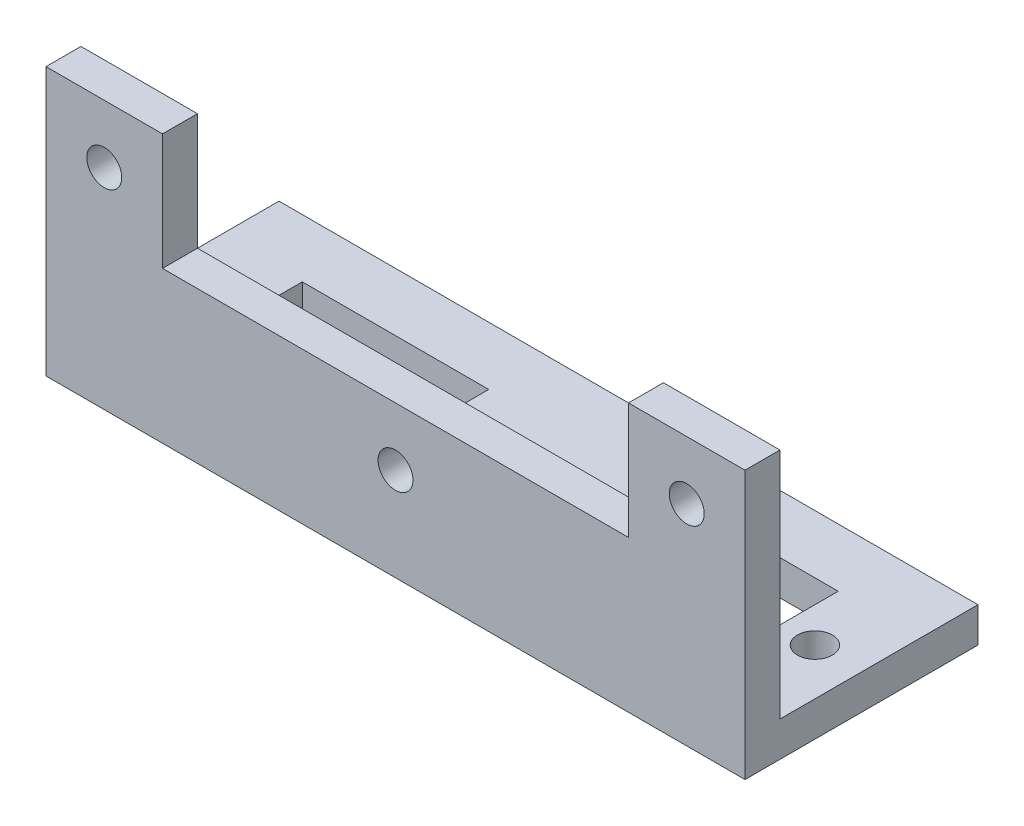
SolidWorks part; units mm, degrees
ref_plane "Front Plane" through (0, 0, 0) normal (0, 0, 1) x (1, 0, 0)
ref_plane "Top Plane" through (0, 0, 0) normal (0, 1, 0) x (1, 0, 0)
ref_plane "Right Plane" through (0, 0, 0) normal (1, 0, 0) x (0, 0, -1)
sketch "Sketch1" plane through (0, 0, 0) normal (0, 1, 0) x (1, 0, 0)
  line L0 (0, 127) -> (-76.2, 127)
  line L1 (0, 0) -> (406.4, 0)
  line L2 (0, 0) -> (0, 254)
  line L3 (0, 254) -> (406.4, 254)
  line L4 (406.4, 0) -> (406.4, 254)
  line L5 (406.4, 127) -> (482.6, 127)
  line L6 (482.6, 127) -> (685.8, 127)
  line L7 (762, 127) -> (685.8, 127)
  line L8 (1168.4, 127) -> (1244.6, 127)
  line L9 (762, 0) -> (1168.4, 0)
  line L10 (762, 0) -> (762, 254)
  line L11 (1168.4, 0) -> (1168.4, 254)
  line L12 (762, 254) -> (1168.4, 254)
  line L13 (-114.3, 127) -> (-177.8, 127)
  line L14 (-177.8, 127) -> (-177.8, 381)
  line L15 (1282.7, 127) -> (1346.2, 127)
  line L16 (1346.2, 127) -> (1346.2, -127)
  line L18 (-177.8, 381) -> (1346.2, 381)
  line L19 (-177.8, 381) -> (-177.8, -127)
  line L20 (-177.8, -127) -> (1346.2, -127)
  line L21 (1346.2, 381) -> (1346.2, -127)
  circle A0 centre (-76.2, 127) radius 38.1
  circle A1 centre (482.6, 127) radius 38.1
  circle A2 centre (1244.6, 127) radius 38.1
  circle A3 centre (685.8, 127) radius 38.1
extrude "Boss-Extrude2" add sketch "Sketch1" along normal blind 76.2 contours A3 L7 L10 L12 L11 L8 A2 L15 L21 L18 L14 L13 A0 L0 L2 L3 L4 L5 A1 L6 | A3 L6 A1 L5 L4 L1 L2 L0 A0 L13 L19 L20 L16 L15 A2 L8 L11 L9 L10 L7 region at (584.2, 0, 27.5366) region at (584.2, 0, -281.5366)
scale "Scale2" scale about centroid uniform scaling yes scale factor 0.03937
sketch "Sketch2" plane through (0, 39.6, 0) normal (0, 1, 0) x (1, 0, 0)
  line L0 (569.2, 132) -> (569.2, 122)
  line L1 (561.2, 132) -> (577.2, 132) construction
  line L2 (561.2, 122) -> (577.2, 122) construction
  line L3 (599.2, 132) -> (599.2, 122)
  line L4 (591.2, 132) -> (607.2, 132) construction
  line L5 (591.2, 122) -> (607.2, 122) construction
  line L6 (569.2, 127) -> (599.2, 127)
sketch "Sketch3" plane through (0, 0, -117) normal (0, 0, 1) x (1, 0, 0)
  line L0 (554.2, 49.6) -> (554.2, 59.6)
  line L1 (554.2, 39.6) -> (614.2, 39.6)
  line L2 (554.2, 39.6) -> (554.2, 49.6)
  line L3 (554.2, 49.6) -> (614.2, 49.6)
  line L4 (614.2, 39.6) -> (614.2, 49.6)
  line L5 (554.2, 59.6) -> (564.2, 59.6)
  line L6 (564.2, 59.6) -> (564.2, 49.6)
  line L7 (584.2, 39.6) -> (584.2, 44.6)
  line L8 (614.2, 49.6) -> (604.2, 49.6)
  line L9 (614.2, 49.6) -> (614.2, 59.6)
  line L10 (614.2, 59.6) -> (604.2, 59.6)
  line L11 (604.2, 49.6) -> (604.2, 59.6)
  line L12 (559.2, 59.6) -> (559.2, 54.6)
  line L13 (609.2, 59.6) -> (609.2, 54.6)
  circle A3 centre (584.2, 44.6) radius 1.5
  circle A4 centre (559.2, 54.6) radius 1.5
  circle A5 centre (609.2, 54.6) radius 1.5
  line M11 (614.2, 39.6) -> (554.2, 39.6)
extrude "Boss-Extrude3" add sketch "Sketch3" against normal blind 3 contours A3 L4 L3 L2 L1 M11 | A4 L5 L0 L3 L6 | A5 L10 L11 L3 L9 region at (559.2, 48.9917, -117) region at (554.3414, 54.6, -117) region at (604.3414, 54.6, -117)
sketch "Sketch4" plane through (0, 0, -120) normal (0, 0, -1) x (-1, 0, 0)
  line L0 (-584.2, 39.6) -> (-584.2, 44.6)
  line L1 (-614.2, 39.6) -> (-554.2, 39.6) construction
  line L2 (-559.2, 54.6) -> (-559.2, 39.6)
